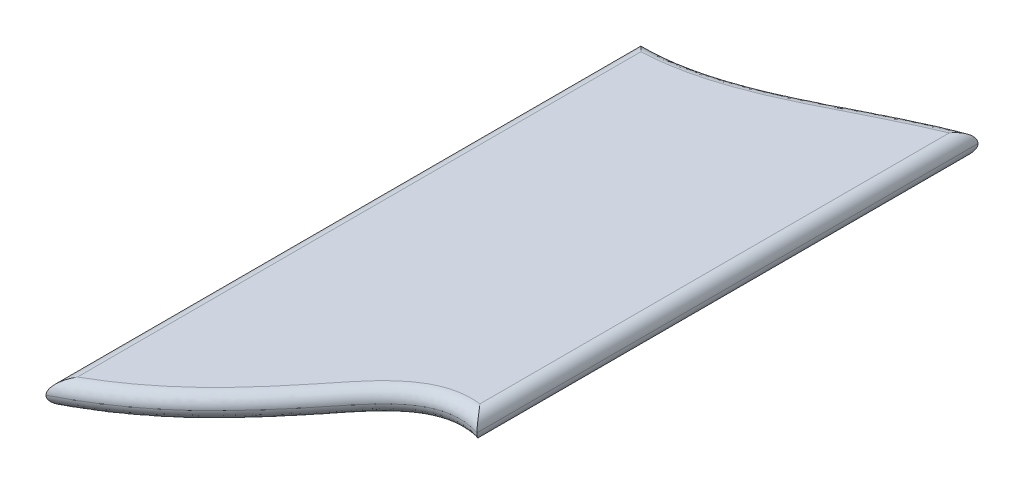
SolidWorks part; units mm, degrees
ref_plane "Front Plane" through (0, 0, 0) normal (0, 0, 1) x (1, 0, 0)
ref_plane "Top Plane" through (0, 0, 0) normal (0, 1, 0) x (1, 0, 0)
ref_plane "Right Plane" through (0, 0, 0) normal (1, 0, 0) x (0, 0, -1)
sketch "Sketch1" plane through (0, 0, 0) normal (0, 1, 0) x (1, 0, 0)
  line L0 (280.6835, 135.3328) -> (280.6835, 50.5191)
  line L1 (238.6854, 120.2785) -> (238.6854, 19.5809)
  spline S0 degree 3 poles (238.6854, 120.2785) (254.1677, 119.9061) (266.7681, 130.5) (280.6835, 135.3328) knots 0 0 0 0 1 1 1 1
  spline S1 degree 3 poles (280.6835, 50.5191) (272.8146, 53.1166) (260.8171, 36.6732) (249.6281, 25.0416) (238.6854, 19.5809) knots 0 0 0 0 0.379628 1 1 1 1
extrude "Boss-Extrude1" add sketch "Sketch1" along normal blind 4
ref_axis "Axis5" through (280.6835, 2, -50.5191) along (0, 0, -1)
fillet "Fillet1" radius 2 8 edges at (280.6835, 0, -92.926) (238.6854, 0, -69.9297) (238.6854, 4, -69.9297) (280.6835, 4, -92.926)
ref_axis "Axis6" through (238.6854, 2, -19.5809) along (0, 0, -1)
ref_plane "Plane1" through (0, 0, -102) normal (0, 0, 1) x (1, 0, 0)
ref_axis "Axis7" through (280.6835, 2, -135.3328) along (0, 1, 0)
